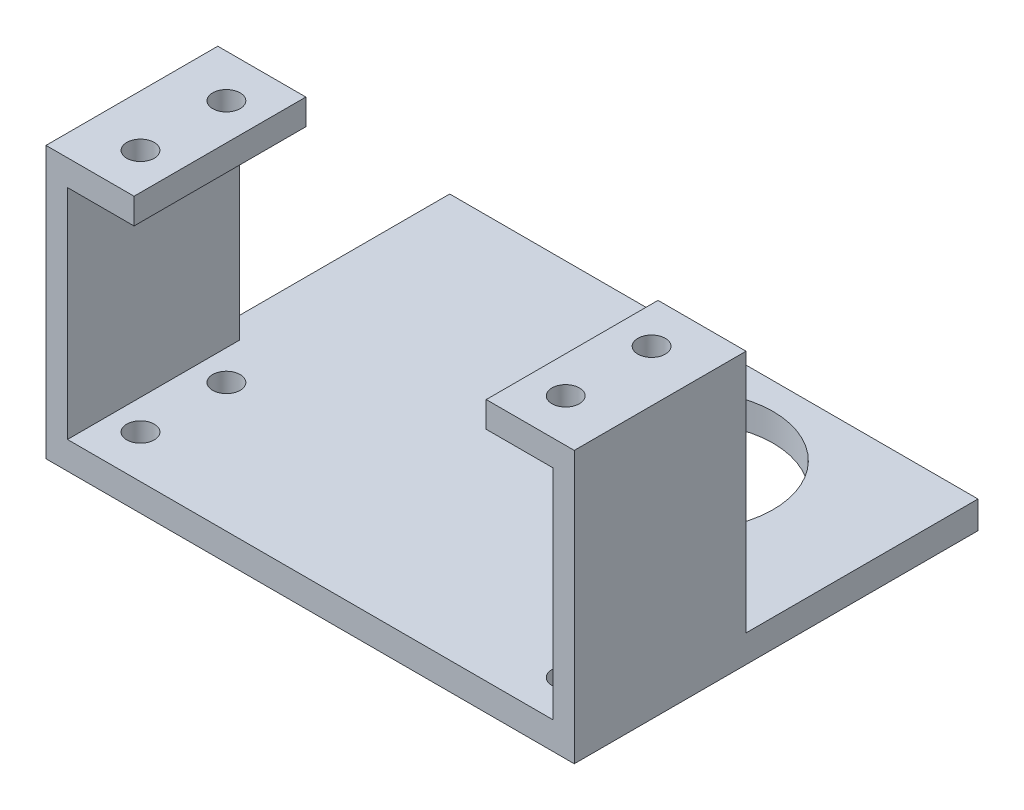
SolidWorks part; units mm, degrees
ref_plane "Front Plane" through (0, 0, 0) normal (0, 0, 1) x (1, 0, 0)
ref_plane "Top Plane" through (0, 0, 0) normal (0, 1, 0) x (1, 0, 0)
ref_plane "Right Plane" through (0, 0, 0) normal (1, 0, 0) x (0, 0, -1)
ref_plane "Plate Bottom" through (0, 14, 0) normal (0, 1, 0) x (1, 0, 0)
sketch "Plate Sketch" plane through (0, 14, 0) normal (0, 1, 0) x (1, 0, 0)
  line L0 (-40.75, 13) -> (20.75, 13)
  line L1 (20.75, 13) -> (20.75, -34)
  line L2 (20.75, -34) -> (-40.75, -34)
  line L3 (-40.75, -34) -> (-40.75, 13)
extrude "Plate" add sketch "Plate Sketch" along normal blind 3.2
ref_axis "Engine Axis" through (23.825, 0, 0) along (-1, 0, 0)
ref_plane "Post Plane" through (0, 0, 14) normal (0, 0, 1) x (1, 0, 0)
sketch "Posts Sketch" plane through (0, 0, 14) normal (0, 0, 1) x (1, 0, 0)
  line L0 (-40.75, 17.2) -> (-38.25, 17.2)
  line L1 (-38.25, 17.2) -> (-38.25, 42.6)
  line L2 (-38.25, 42.6) -> (-30.5, 42.6)
  line L3 (-30.5, 42.6) -> (-30.5, 45.6)
  line L4 (-30.5, 45.6) -> (-40.75, 45.6)
  line L5 (-40.75, 45.6) -> (-40.75, 17.2)
  line L6 (20.75, 17.2) -> (18.25, 17.2)
  line L7 (18.25, 17.2) -> (18.25, 42.6)
  line L8 (18.25, 42.6) -> (10.5, 42.6)
  line L9 (10.5, 42.6) -> (10.5, 45.6)
  line L10 (10.5, 45.6) -> (20.75, 45.6)
  line L11 (20.75, 45.6) -> (20.75, 17.2)
extrude "Posts" add sketch "Posts Sketch" along normal blind 20
sketch "Servo Holes Sketch" plane through (0, 0, 0) normal (0, 1, 0) x (1, 0, 0)
  circle A0 centre (-34.75, -19) radius 1.6
  circle A1 centre (-34.75, -29) radius 1.6
  circle A2 centre (14.75, -19) radius 1.6
  circle A3 centre (14.75, -29) radius 1.6
extrude "Servo Holes" cut sketch "Servo Holes Sketch" against normal mid plane 106.2
sketch "Panel Hole Sketch" plane through (0, 0, 0) normal (0, 1, 0) x (1, 0, 0)
  circle A0 centre (0, 0) radius 9.9
extrude "Panel Hole" cut sketch "Panel Hole Sketch" against normal mid plane 36.4
